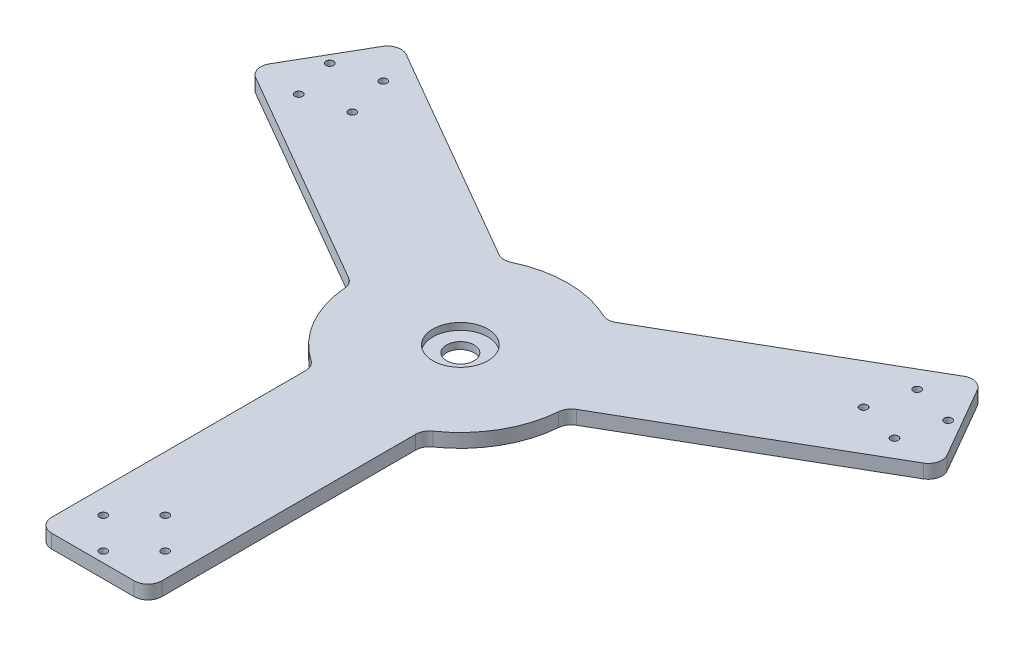
SolidWorks part; units mm, degrees
ref_plane "Front Plane" through (0, 0, 0) normal (0, 0, 1) x (1, 0, 0)
ref_plane "Top Plane" through (0, 0, 0) normal (0, 1, 0) x (1, 0, 0)
ref_plane "Right Plane" through (0, 0, 0) normal (1, 0, 0) x (0, 0, -1)
sketch "Sketch1" plane through (0, 0, 0) normal (0, 1, 0) x (1, 0, 0)
  circle A0 centre (0, 0) radius 78
  dimension "D1" = 156
extrude "Boss-Extrude1" add sketch "Sketch1" along normal blind 10
sketch "Sketch4" plane through (0, 0, 0) normal (0, -1, 0) x (1, 0, 0)
  line L0 (-40, 66.9627) -> (-40, 266.9627)
  line L1 (-40, 266.9627) -> (40, 266.9627)
  line L2 (40, 266.9627) -> (40, 66.9627)
  arc A0 (-40, 66.9627) -> (40, 66.9627) centre (0, 0) cw
  circle A1 centre (0, 0) radius 78 construction
  point P3 (0, 266.9627)
  dimension "D1" = 80
  dimension "D2" = 200
extrude "Boss-Extrude2" add sketch "Sketch4" against normal up to surface (10 mm away) up to face at (0, 10, 78)
ref_axis "Axis1" through (0, 28.9443, 0) along (0, -1, 0)
fillet "Fillet1" radius 10 4 edges at (-40, 5, 66.9627) (-40, 5, 266.9627) (40, 5, 266.9627) (40, 5, 66.9627)
sketch "Sketch7" plane through (0, 10, 0) normal (0, 1, 0) x (1, 0, 0)
  line L0 (0, -214.4627) -> (0, -259.4627) construction
  line L2 (-22.5, -236.9627) -> (22.5, -236.9627) construction
  line L4 (30, -266.9627) -> (-30, -266.9627) construction
  point P0 (0, -259.4627)
  point P2 (-22.5, -236.9627)
  point P4 (22.5, -236.9627)
  point P6 (0, -214.4627)
  point P17 (0, -236.9627)
  point P18 (0, -236.9627)
  point P21 (0, -266.9627)
  dimension "D1" = 45
  dimension "D2" = 7.5
hole_wizard "M5 Clearance Hole1" positions "Sketch7" profile "Sketch6" hole size "M5" standard "ANSI Metric" end condition through all
sketch "Sketch6" plane through (0, 10, 259.4627) normal (1, 0, 0) x (0, 0, 1)
  line L0 (0, 0) -> (0, 10)
  line L1 (0, 10) -> (2.75, 10)
  line L2 (2.75, 10) -> (2.75, 0.025)
  line L3 (2.75, 0.025) -> (2.775, 0)
  line L5 (2.775, 0) -> (0, 0)
  line L6 (-2.75, 0.025) -> (-2.775, 0) construction
  line L11 (0, -6.35) -> (0, 107.95) construction
  dimension "Thru Hole Dia." = 5.5
  dimension "Thru Hole Depth" = 10
  dimension "Near C'Sink Dia." = 5.55
  dimension "Near C'Sink Angle" = 90
pattern_circular "CirPattern1" count 3 over 360 about axis through (0, 28.9443, 0) along (0, -1, 0) of "Boss-Extrude2", "Fillet1", "M5 Clearance Hole1"
sketch "Sketch11" plane through (0, 10, 0) normal (0, 1, 0) x (1, 0, 0)
  point P0 (0, 0)
hole_wizard "Hole1" positions "Sketch11" profile "Sketch10" legacy end condition through all
sketch "Sketch10" plane through (0, 10, 0) normal (1, 0, 0) x (0, 0, 1)
  line L0 (0, 0) -> (0, 10)
  line L1 (0, 10) -> (10, 10)
  line L2 (10, 10) -> (10, 5)
  line L3 (10, 5) -> (20, 5)
  line L4 (20, 5) -> (20, 0)
  line L5 (20, 0) -> (0, 0)
  line L6 (0, 110) -> (0, -10) construction
  dimension "Diameter" = 20
  dimension "Depth" = 10
  dimension "C-Bore Diameter" = 40
  dimension "C-Bore Depth" = 5
